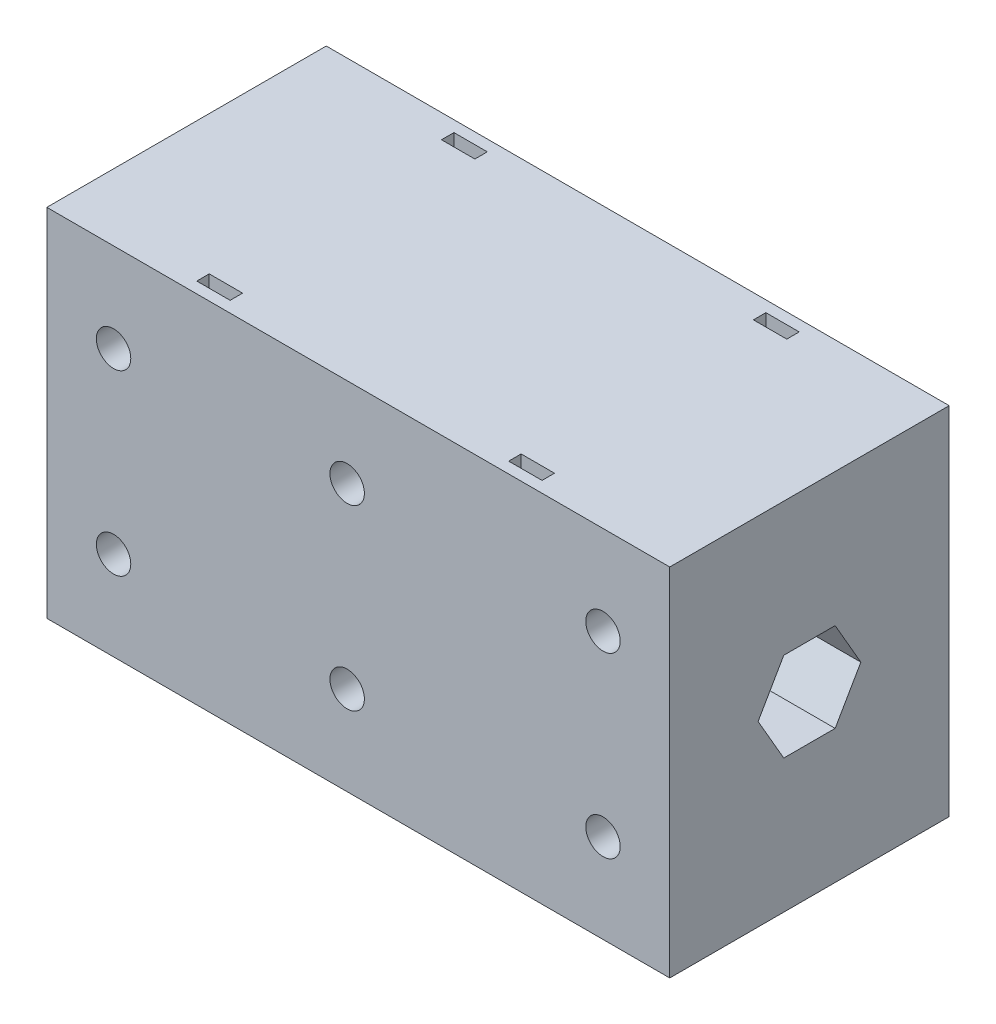
SolidWorks part; units mm, degrees
material "6061-T6 (SS)"
ref_plane "Front" through (0, 0, 0) normal (0, 0, 1) x (1, 0, 0)
ref_plane "Top" through (0, 0, 0) normal (0, 1, 0) x (1, 0, 0)
ref_plane "Right" through (0, 0, 0) normal (1, 0, 0) x (0, 0, -1)
sketch "Sketch1" plane through (0, 0, 0) normal (1, 0, 0) x (0, 0, -1)
  line L1 (19.939, -25.4) -> (-19.939, -25.4)
  line L2 (19.939, -25.4) -> (19.939, 25.4)
  line L3 (19.939, 25.4) -> (-19.939, 25.4)
  line L4 (-19.939, -25.4) -> (-19.939, 25.4)
  line L5 (19.939, -25.4) -> (-19.939, 25.4) construction
  line L6 (19.939, 25.4) -> (-19.939, -25.4) construction
  point P0 (0, 0)
  dimension "D1" = 50.8
  dimension "D2" = 39.878
extrude "Boss-Extrude1" add sketch "Sketch1" along normal blind 88.9
sketch "Sketch3" plane through (88.9, 0, 0) normal (1, 0, 0) x (0, 0, -1)
  line L1 (7.3323, 0) -> (3.6662, 6.35)
  line L2 (3.6662, 6.35) -> (-3.6662, 6.35)
  line L3 (-3.6662, 6.35) -> (-7.3323, 0)
  line L4 (-7.3323, 0) -> (-3.6662, -6.35)
  line L5 (-3.6662, -6.35) -> (3.6662, -6.35)
  line L6 (3.6662, -6.35) -> (7.3323, 0)
  circle A0 centre (0, 0) radius 6.35 construction
  dimension "D1" = 12.7
extrude "Cut-Extrude2" cut sketch "Sketch3" against normal through all
ref_axis "Axis1" through (-80.9, 0, 0) along (1, 0, 0)
sketch "Sketch4" plane through (0, 25.4, 0) normal (0, 1, 0) x (1, 0, 0)
  line L1 (19.812, -18.3515) -> (24.5745, -18.3515)
  line L2 (19.812, -18.3515) -> (19.812, -16.5735)
  line L3 (19.812, -16.5735) -> (24.5745, -16.5735)
  line L4 (24.5745, -18.3515) -> (24.5745, -16.5735)
  line L5 (19.812, -18.3515) -> (24.5745, -16.5735) construction
  line L6 (19.812, -16.5735) -> (24.5745, -18.3515) construction
  line L7 (64.3255, -16.5735) -> (69.088, -16.5735)
  line L8 (64.3255, -16.5735) -> (64.3255, -18.3515)
  line L9 (64.3255, -18.3515) -> (69.088, -18.3515)
  line L10 (69.088, -16.5735) -> (69.088, -18.3515)
  line L11 (64.3255, -16.5735) -> (69.088, -18.3515) construction
  line L12 (64.3255, -18.3515) -> (69.088, -16.5735) construction
  line L13 (64.3255, 18.3515) -> (69.088, 18.3515)
  line L14 (64.3255, 18.3515) -> (64.3255, 16.5735)
  line L15 (64.3255, 16.5735) -> (69.088, 16.5735)
  line L16 (69.088, 18.3515) -> (69.088, 16.5735)
  line L17 (64.3255, 18.3515) -> (69.088, 16.5735) construction
  line L18 (64.3255, 16.5735) -> (69.088, 18.3515) construction
  line L19 (19.812, 18.3515) -> (24.5745, 18.3515)
  line L20 (19.812, 18.3515) -> (19.812, 16.5735)
  line L21 (19.812, 16.5735) -> (24.5745, 16.5735)
  line L22 (24.5745, 18.3515) -> (24.5745, 16.5735)
  line L23 (19.812, 18.3515) -> (24.5745, 16.5735) construction
  line L24 (19.812, 16.5735) -> (24.5745, 18.3515) construction
  line L25 (88.9, 19.939) -> (88.9, -19.939) construction
  line L26 (0, 19.939) -> (0, -19.939) construction
  line L27 (88.9, 19.939) -> (0, 19.939) construction
  line L28 (88.9, -19.939) -> (0, -19.939) construction
  point P0 (22.1933, -17.4625)
  point P5 (66.7067, -17.4625)
  point P10 (66.7067, 17.4625)
  point P15 (22.1932, 17.4625)
  dimension "D1" = 19.812
  dimension "D2" = 4.7625
  dimension "D3" = 1.778
  dimension "D4" = 19.812
  dimension "D5" = 1.5875
  dimension "D6" = 1.5875
extrude "Cut-Extrude3" cut sketch "Sketch4" against normal through all
sketch "Sketch7" plane through (0, 0, 19.939) normal (0, 0, 1) x (1, 0, 0)
  line L0 (88.9, 25.4) -> (0, 25.4) construction
  line L1 (0, 25.4) -> (0, -25.4) construction
  line L2 (88.9, 25.4) -> (88.9, -25.4) construction
  point P0 (9.525, 12.7)
  point P2 (42.861, 12.7)
  point P4 (79.375, 12.7)
  point P6 (79.375, -12.7)
  point P8 (42.861, -12.7)
  point P10 (9.525, -12.7)
  dimension "D1" = 25.4
  dimension "D2" = 12.7
  dimension "D3" = 9.525
  dimension "D4" = 9.525
hole_wizard "#10 (0.1935) Diameter Hole1" positions "Sketch7" profile "Sketch6" hole size "#10" standard "ANSI Inch" end condition up to next
sketch "Sketch6" plane through (9.525, 12.7, 19.939) normal (1, 0, 0) x (0, -1, 0)
  line L0 (0, 0) -> (0, 39.878)
  line L1 (0, 39.878) -> (2.4574, 39.878)
  line L2 (2.4574, 39.878) -> (2.4574, 0)
  line L5 (2.4574, 0) -> (0, 0)
  line L11 (0, -6.35) -> (0, 107.95) construction
  dimension "Thru Hole Dia." = 4.9149
  dimension "Thru Hole Depth" = 39.878
